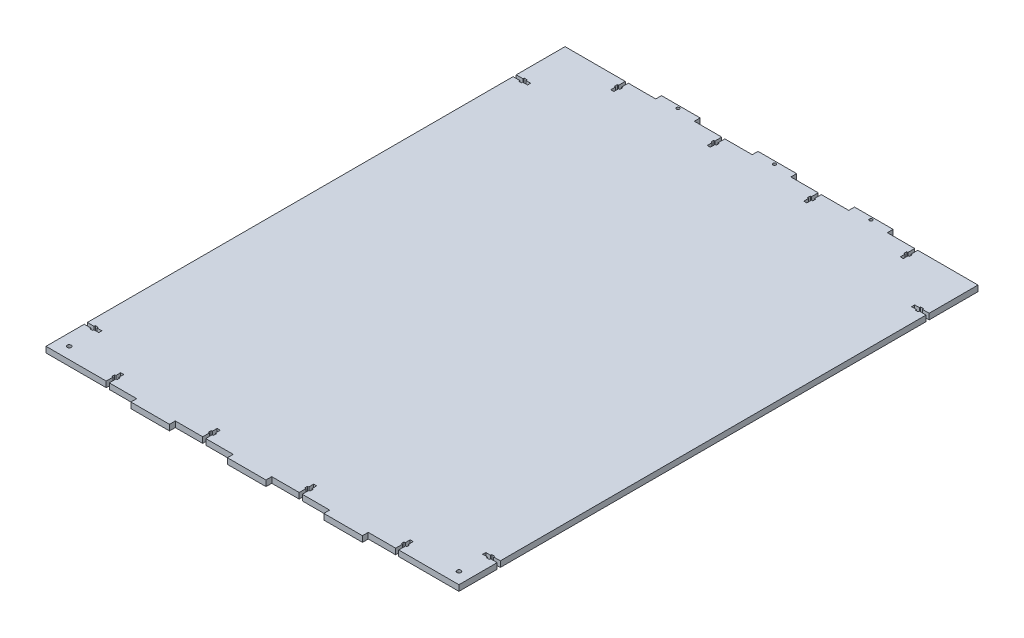
SolidWorks part; units mm, degrees
ref_plane "Front Plane" through (0, 0, 0) normal (0, 0, 1) x (1, 0, 0)
ref_plane "Top Plane" through (0, 0, 0) normal (0, 1, 0) x (1, 0, 0)
ref_plane "Right Plane" through (0, 0, 0) normal (1, 0, 0) x (0, 0, -1)
sketch "Sketch1" plane through (0, 0, 0) normal (0, 1, 0) x (1, 0, 0)
  line L1 (-214, -269) -> (214, -269)
  line L2 (-214, -269) -> (-214, 269)
  line L3 (-214, 269) -> (214, 269)
  line L4 (214, -269) -> (214, 269)
  line L5 (-214, -269) -> (214, 269) construction
  line L6 (-214, 269) -> (214, -269) construction
  point P0 (0, 0)
  dimension "D1" = 428
  dimension "D2" = 538
extrude "Boss-Extrude1" add sketch "Sketch1" along normal blind 6
sketch "Sketch2" plane through (0, 0, 0) normal (0, -1, 0) x (1, 0, 0)
  line L14 (0, 0) -> (0, 133.2527) construction
  line L15 (0, 0) -> (-145.1849, 0) construction
  line L40 (-148.4, 275) -> (-151.6, 275) construction
  line L41 (-148.4, 275) -> (-151.6, 275) construction
  line L42 (-48.4, 275) -> (-51.6, 275) construction
  line L43 (-48.4, 275) -> (-51.6, 275) construction
  line L44 (-148.4, 275) -> (-51.6, 275) construction
  line L45 (-214, 269) -> (214, 269) construction
  line L46 (-120, 275) -> (-80, 275)
  line L47 (-120, 275) -> (-120, 269)
  line L48 (-120, 269) -> (-80, 269)
  line L49 (-80, 275) -> (-80, 269)
  line L50 (-20, 269) -> (20, 269)
  line L51 (20, 275) -> (20, 269)
  line L52 (-20, 275) -> (20, 275)
  line L53 (-20, 275) -> (-20, 269)
  line L54 (80, 269) -> (120, 269)
  line L55 (120, 275) -> (120, 269)
  line L56 (80, 275) -> (120, 275)
  line L57 (80, 275) -> (80, 269)
  line L58 (120, -275) -> (120, -269)
  line L59 (80, -269) -> (120, -269)
  line L60 (80, -275) -> (120, -275)
  line L61 (80, -275) -> (80, -269)
  line L62 (20, -275) -> (20, -269)
  line L63 (-20, -275) -> (20, -275)
  line L64 (-20, -269) -> (20, -269)
  line L65 (-20, -275) -> (-20, -269)
  line L66 (-120, -269) -> (-80, -269)
  line L67 (-120, -275) -> (-120, -269)
  line L68 (-120, -275) -> (-80, -275)
  line L69 (-80, -275) -> (-80, -269)
  point P50 (-100, 275)
  dimension "D3" = 40
  dimension "D4" = 3
extrude "Boss-Extrude2" add sketch "Sketch2" against normal blind 6
sketch "Sketch3" plane through (0, 0, 0) normal (0, -1, 0) x (1, 0, 0)
  line L0 (207, -219.55) -> (207, -218.35)
  line L1 (-214, -218.35) -> (-214, -215.15) construction
  line L2 (-214, -218.35) -> (-214, -215.15) construction
  line L3 (207, -219.55) -> (204, -219.55)
  line L4 (204, -219.55) -> (204, -218.35)
  line L5 (204, -218.35) -> (199, -218.35)
  line L6 (-214, 226.15) -> (-214, 229.35) construction
  line L7 (-214, 226.15) -> (-214, 229.35) construction
  line L8 (-214, -216.75) -> (-199, -216.75) construction
  line L9 (-214, 227.75) -> (-199, 227.75) construction
  line L10 (-214, 226.15) -> (-207, 226.15)
  line L11 (-214, -218.35) -> (-207, -218.35)
  line L12 (-214, 229.35) -> (-207, 229.35)
  line L13 (-214, -215.15) -> (-207, -215.15)
  line L14 (-214, 226.15) -> (-214, 229.35)
  line L15 (-199, 226.15) -> (-199, 229.35)
  line L16 (-214, -218.35) -> (-214, -215.15)
  line L17 (-199, -218.35) -> (-199, -215.15)
  line L18 (-207, 229.35) -> (-207, 230.55)
  line L19 (-207, -219.55) -> (-204, -219.55)
  line L20 (-207, -219.55) -> (-207, -218.35)
  line L21 (-207, -213.95) -> (-204, -213.95)
  line L22 (199, -218.35) -> (199, -215.15)
  line L23 (-204, -219.55) -> (-204, -218.35)
  line L24 (-207, -219.55) -> (-204, -213.95) construction
  line L25 (-207, -213.95) -> (-204, -219.55) construction
  line L26 (-207, 224.95) -> (-204, 224.95)
  line L27 (-207, 224.95) -> (-207, 226.15)
  line L28 (-207, 230.55) -> (-204, 230.55)
  line L29 (-204, 224.95) -> (-204, 226.15)
  line L30 (-207, 224.95) -> (-204, 230.55) construction
  line L31 (-207, 230.55) -> (-204, 224.95) construction
  line L32 (-204, 229.35) -> (-199, 229.35)
  line L33 (-214, 229.35) -> (-199, 229.35) construction
  line L34 (-204, 226.15) -> (-199, 226.15)
  line L35 (-214, 226.15) -> (-199, 226.15) construction
  line L36 (-204, 229.35) -> (-204, 230.55)
  line L37 (-204, -215.15) -> (-204, -213.95)
  line L38 (-204, -218.35) -> (-199, -218.35)
  line L39 (-214, -218.35) -> (-199, -218.35) construction
  line L40 (-207, -215.15) -> (-207, -213.95)
  line L41 (-204, -215.15) -> (-199, -215.15)
  line L42 (-214, -215.15) -> (-199, -215.15) construction
  line L43 (204, -215.15) -> (199, -215.15)
  line L44 (204, -215.15) -> (204, -213.95)
  line L45 (207, -213.95) -> (204, -213.95)
  line L46 (207, -215.15) -> (207, -213.95)
  line L47 (214, -215.15) -> (207, -215.15)
  line L48 (214, -218.35) -> (214, -215.15)
  line L49 (214, -218.35) -> (207, -218.35)
  line L50 (214, 226.15) -> (207, 226.15)
  line L51 (207, 224.95) -> (207, 226.15)
  line L52 (207, 224.95) -> (204, 224.95)
  line L53 (204, 224.95) -> (204, 226.15)
  line L54 (204, 226.15) -> (199, 226.15)
  line L55 (199, 226.15) -> (199, 229.35)
  line L56 (204, 229.35) -> (199, 229.35)
  line L57 (204, 229.35) -> (204, 230.55)
  line L58 (207, 230.55) -> (204, 230.55)
  line L59 (207, 229.35) -> (207, 230.55)
  line L60 (214, 226.15) -> (214, 229.35)
  line L61 (214, 229.35) -> (207, 229.35)
  line L62 (-120, -272) -> (-80, -272) construction
  line L63 (0, 0) -> (160.2761, 0) construction
  line L64 (147.2, 259) -> (152.8, 262) construction
  line L65 (-120, -269) -> (-120, -275) construction
  line L66 (-80, -275) -> (-80, -269) construction
  line L67 (147.2, 262) -> (152.8, 259) construction
  line L68 (148.4, 269) -> (151.6, 254) construction
  line L69 (148.4, 254) -> (151.6, 269) construction
  line L70 (47.2, 259) -> (52.8, 262) construction
  line L71 (47.2, 262) -> (52.8, 259) construction
  line L72 (48.4, 269) -> (51.6, 254) construction
  line L73 (48.4, 254) -> (51.6, 269) construction
  line L74 (151.6, 259) -> (152.8, 259)
  line L75 (151.6, 262) -> (151.6, 269)
  line L76 (148.4, 262) -> (148.4, 269)
  line L77 (152.8, 262) -> (152.8, 259)
  line L78 (147.2, 259) -> (148.4, 259)
  line L79 (147.2, 262) -> (147.2, 259)
  line L80 (147.2, 262) -> (148.4, 262)
  line L81 (151.6, 262) -> (152.8, 262)
  line L82 (151.6, 254) -> (151.6, 259)
  line L83 (148.4, 269) -> (151.6, 269)
  line L84 (148.4, 254) -> (148.4, 259)
  line L85 (148.4, 254) -> (151.6, 254)
  line L86 (0, 0) -> (0, 128.8409) construction
  line L87 (51.6, 259) -> (52.8, 259)
  line L88 (51.6, 262) -> (51.6, 269)
  line L89 (48.4, 262) -> (48.4, 269)
  line L90 (52.8, 262) -> (52.8, 259)
  line L91 (47.2, 259) -> (48.4, 259)
  line L92 (47.2, 262) -> (47.2, 259)
  line L93 (47.2, 262) -> (48.4, 262)
  line L94 (51.6, 262) -> (52.8, 262)
  line L95 (51.6, 254) -> (51.6, 259)
  line L96 (48.4, 269) -> (51.6, 269)
  line L97 (48.4, 254) -> (48.4, 259)
  line L98 (48.4, 254) -> (51.6, 254)
  line L99 (-52.8, 259) -> (-47.2, 262) construction
  line L100 (-52.8, 262) -> (-47.2, 259) construction
  line L101 (-51.6, 269) -> (-48.4, 254) construction
  line L102 (-51.6, 254) -> (-48.4, 269) construction
  line L103 (-152.8, 259) -> (-147.2, 262) construction
  line L104 (-152.8, 262) -> (-147.2, 259) construction
  line L105 (-151.6, 269) -> (-148.4, 254) construction
  line L106 (-151.6, 254) -> (-148.4, 269) construction
  line L107 (-48.4, 259) -> (-47.2, 259)
  line L108 (-48.4, 262) -> (-48.4, 269)
  line L109 (-51.6, 262) -> (-51.6, 269)
  line L110 (-47.2, 262) -> (-47.2, 259)
  line L111 (-52.8, 259) -> (-51.6, 259)
  line L112 (-52.8, 262) -> (-52.8, 259)
  line L113 (-52.8, 262) -> (-51.6, 262)
  line L114 (-48.4, 262) -> (-47.2, 262)
  line L115 (-48.4, 254) -> (-48.4, 259)
  line L116 (-51.6, 269) -> (-48.4, 269)
  line L117 (-51.6, 254) -> (-51.6, 259)
  line L118 (-51.6, 254) -> (-48.4, 254)
  line L119 (-148.4, 259) -> (-147.2, 259)
  line L120 (-148.4, 262) -> (-148.4, 269)
  line L121 (-151.6, 262) -> (-151.6, 269)
  line L122 (-147.2, 262) -> (-147.2, 259)
  line L123 (-152.8, 259) -> (-151.6, 259)
  line L124 (-152.8, 262) -> (-152.8, 259)
  line L125 (-152.8, 262) -> (-151.6, 262)
  line L126 (-148.4, 262) -> (-147.2, 262)
  line L127 (-148.4, 254) -> (-148.4, 259)
  line L128 (-151.6, 269) -> (-148.4, 269)
  line L129 (-151.6, 254) -> (-151.6, 259)
  line L130 (-151.6, 254) -> (-148.4, 254)
  line L166 (-151.6, -275) -> (-148.4, -275) construction
  line L167 (-151.6, -275) -> (-148.4, -275) construction
  line L168 (-150, -275) -> (-150, -234.6121) construction
  line L169 (-120, -269) -> (-214, -269) construction
  line L170 (-151.6, -254) -> (-148.4, -254)
  line L171 (-151.6, -254) -> (-151.6, -259)
  line L172 (-151.6, -269) -> (-148.4, -269)
  line L173 (-148.4, -254) -> (-148.4, -259)
  line L174 (-151.6, -254) -> (-148.4, -269) construction
  line L175 (-151.6, -269) -> (-148.4, -254) construction
  line L176 (-148.4, -262) -> (-147.2, -262)
  line L177 (-152.8, -262) -> (-151.6, -262)
  line L178 (-152.8, -262) -> (-152.8, -259)
  line L179 (-152.8, -259) -> (-151.6, -259)
  line L180 (-147.2, -262) -> (-147.2, -259)
  line L181 (-152.8, -262) -> (-147.2, -259) construction
  line L182 (-152.8, -259) -> (-147.2, -262) construction
  line L183 (-151.6, -262) -> (-151.6, -269)
  line L184 (-148.4, -262) -> (-148.4, -269)
  line L185 (-148.4, -259) -> (-147.2, -259)
  line L186 (-51.6, -254) -> (-48.4, -254)
  line L187 (-51.6, -254) -> (-51.6, -259)
  line L188 (-51.6, -269) -> (-48.4, -269)
  line L189 (-48.4, -254) -> (-48.4, -259)
  line L190 (-48.4, -262) -> (-47.2, -262)
  line L191 (-52.8, -262) -> (-51.6, -262)
  line L192 (-52.8, -262) -> (-52.8, -259)
  line L193 (-52.8, -259) -> (-51.6, -259)
  line L194 (-47.2, -262) -> (-47.2, -259)
  line L195 (-51.6, -262) -> (-51.6, -269)
  line L196 (-48.4, -262) -> (-48.4, -269)
  line L197 (-48.4, -259) -> (-47.2, -259)
  line L198 (-51.6, -254) -> (-48.4, -269) construction
  line L199 (-51.6, -269) -> (-48.4, -254) construction
  line L200 (-52.8, -262) -> (-47.2, -259) construction
  line L201 (-52.8, -259) -> (-47.2, -262) construction
  line L202 (48.4, -254) -> (51.6, -254)
  line L203 (48.4, -254) -> (48.4, -259)
  line L204 (48.4, -269) -> (51.6, -269)
  line L205 (51.6, -254) -> (51.6, -259)
  line L206 (51.6, -262) -> (52.8, -262)
  line L207 (47.2, -262) -> (48.4, -262)
  line L208 (47.2, -262) -> (47.2, -259)
  line L209 (47.2, -259) -> (48.4, -259)
  line L210 (52.8, -262) -> (52.8, -259)
  line L211 (48.4, -262) -> (48.4, -269)
  line L212 (51.6, -262) -> (51.6, -269)
  line L213 (51.6, -259) -> (52.8, -259)
  line L214 (48.4, -254) -> (51.6, -269) construction
  line L215 (48.4, -269) -> (51.6, -254) construction
  line L216 (47.2, -262) -> (52.8, -259) construction
  line L217 (47.2, -259) -> (52.8, -262) construction
  line L218 (148.4, -254) -> (151.6, -254)
  line L219 (148.4, -254) -> (148.4, -259)
  line L220 (148.4, -269) -> (151.6, -269)
  line L221 (151.6, -254) -> (151.6, -259)
  line L222 (151.6, -262) -> (152.8, -262)
  line L223 (147.2, -262) -> (148.4, -262)
  line L224 (147.2, -262) -> (147.2, -259)
  line L225 (147.2, -259) -> (148.4, -259)
  line L226 (152.8, -262) -> (152.8, -259)
  line L227 (148.4, -262) -> (148.4, -269)
  line L228 (151.6, -262) -> (151.6, -269)
  line L229 (151.6, -259) -> (152.8, -259)
  line L230 (148.4, -254) -> (151.6, -269) construction
  line L231 (148.4, -269) -> (151.6, -254) construction
  line L232 (147.2, -262) -> (152.8, -259) construction
  line L233 (147.2, -259) -> (152.8, -262) construction
  circle A0 centre (-100, -272) radius 1.6
  circle A1 centre (0, -272) radius 1.6
  circle A2 centre (100, -272) radius 1.6
  circle A4 centre (202, 257) radius 2.1 construction
  circle A5 centre (202, 257) radius 2.1
  circle A6 centre (-202, 257) radius 2.1 construction
  circle A7 centre (-202, 257) radius 2.1
  point P25 (-205.5, -216.75)
  point P30 (-205.5, 227.75)
  point P104 (150, 260.5)
  point P105 (150, 261.5)
  point P106 (50, 260.5)
  point P107 (50, 261.5)
  point P132 (-50, 260.5)
  point P133 (-50, 261.5)
  point P134 (-150, 260.5)
  point P135 (-150, 261.5)
  point P154 (-150, -261.5)
  point P161 (-150, -260.5)
  point P171 (-50, -261.5)
  point P176 (-50, -260.5)
  point P185 (50, -261.5)
  point P190 (50, -260.5)
  point P199 (150, -261.5)
  point P204 (150, -260.5)
  line M5 (214, -269) -> (214, 269)
  line M6 (214, 269) -> (120, 269)
  line M10 (80, 269) -> (20, 269)
  line M14 (-20, 269) -> (-80, 269)
  line M18 (-120, 269) -> (-214, 269)
  line M19 (-214, 269) -> (-214, -269)
  line M20 (-214, -269) -> (-120, -269)
  line M24 (-80, -269) -> (-20, -269)
  line M28 (20, -269) -> (80, -269)
  line M32 (120, -269) -> (214, -269)
  dimension "D11" = 3.2
  dimension "D1" = 15
  dimension "D2" = 1.6
  dimension "D3" = 1.6
  dimension "D4" = 7
  dimension "D5" = 5.6
  dimension "D6" = 15
  dimension "D7" = 5.6
  dimension "D8" = 7
  dimension "D10" = 3
  dimension "D13" = 3
  dimension "D9" = 4
  dimension "D12" = 3
extrude "Cut-Extrude1" cut sketch "Sketch3" against normal through all contours L129 L130 L127 L119 L122 L126 L120 L121 L125 L124 L123 M18 | L32 L36 L28 L18 L12 L10 L27 L26 L29 L34 L15 M19 | A7 | L117 L118 L115 L107 L110 L114 L108 L109 L113 L112 L111 M14 | L97 L98 L95 L87 L90 L94 L88 L89 L93 L92 L91 M10 | L84 L85 L82 L74 L77 L81 L75 L76 L80 L79 L78 M6 | A5 | L61 L59 L58 L57 L56 L55 L54 L53 L52 L51 L50 M5 | L229 L221 L218 L219 L225 L224 L223 L227 L228 L222 L226 M32 | A2 | L213 L205 L202 L203 L209 L208 L207 L211 L212 L206 L210 M28 | A1 | L197 L189 L186 L187 L193 L192 L191 L195 L196 L190 L194 M24 | A0 | L185 L173 L170 L171 L179 L178 L177 L183 L184 L176 L180 M20 | L41 L37 L21 L40 L13 L11 L20 L19 L23 L38 L17 M19 | L47 L46 L45 L44 L43 L22 L5 L4 L3 L0 L49 L48 region at (150, 0, 261.3696) region at (206.3696, 0, 227.75) region at (150, 0, -261.3696) region at (-206.3696, 0, 227.75) region at (-150, 0, 261.3696) region at (-150, 0, -261.3696) region at (-206.3696, 0, -216.75) region at (50, 0, 261.3696) region at (-50, 0, 261.3696) region at (-50, 0, -261.3696) region at (50, 0, -261.3696) region at (-100, 0, -272) region at (0, 0, -272) region at (100, 0, -272) region at (202, 0, 257) region at (-202, 0, 257)
